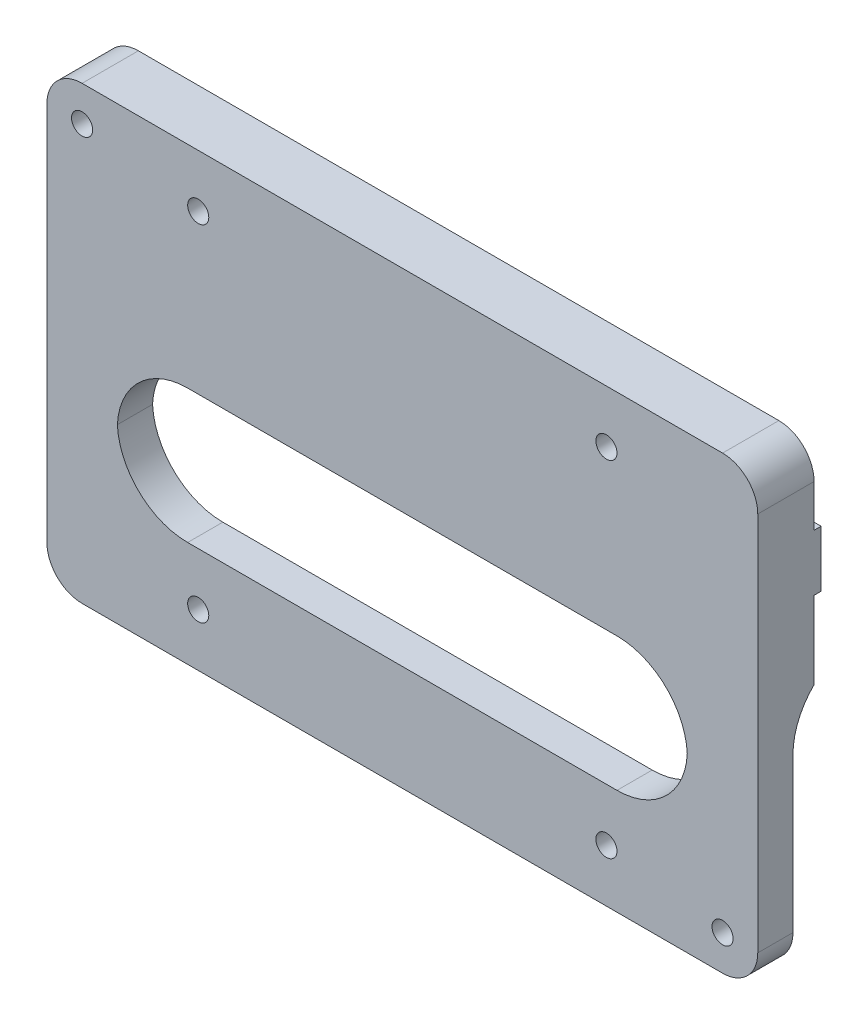
SolidWorks part; units mm, degrees
ref_plane "Top Plane" through (0, 0, 0) normal (0, 0, 1) x (1, 0, 0)
ref_plane "Right Plane" through (0, 0, 0) normal (0, 1, 0) x (1, 0, 0)
ref_plane "Front Plane" through (0, 0, 0) normal (1, 0, 0) x (0, 0, -1)
sketch "Sketch1" plane through (0, 0, 0) normal (0, 0, 1) x (1, 0, 0)
  line L0 (-50.5, 27) -> (-45.5, 27) construction
  line L1 (-29, -24.5) -> (29, -24.5) construction
  line L2 (-29, -24.5) -> (-29, 24.5) construction
  line L3 (-29, 24.5) -> (29, 24.5) construction
  line L4 (29, -24.5) -> (29, 24.5) construction
  line L5 (-29, -24.5) -> (29, 24.5) construction
  line L6 (-29, 24.5) -> (29, -24.5) construction
  line L7 (-50.5, -32) -> (50.5, -32)
  line L8 (-50.5, -32) -> (-50.5, 32)
  line L9 (-50.5, 32) -> (50.5, 32)
  line L10 (50.5, -32) -> (50.5, 32)
  line L11 (-50.5, -32) -> (50.5, 32) construction
  line L12 (-50.5, 32) -> (50.5, -32) construction
  line L13 (-45.5, 27) -> (-45.5, 32) construction
  line L14 (-45.5, 27) -> (45.5, -27) construction
  circle A0 centre (-29, 24.5) radius 1.5
  circle A1 centre (29, 24.5) radius 1.5
  circle A2 centre (29, -24.5) radius 1.5
  circle A3 centre (-29, -24.5) radius 1.5
  circle A4 centre (45.5, -27) radius 1.5
  circle A5 centre (-45.5, 27) radius 1.5
  point P0 (0, 0)
  point P10 (0, 0)
  dimension "D3" = 3
  dimension "D4" = 20
  dimension "D6" = 3
  dimension "D1" = 49
  dimension "D2" = 58
  dimension "D5" = 6
  dimension "D7" = 5
extrude "Boss-Extrude1" add sketch "Sketch1" along normal blind 8
sketch "Sketch2" plane through (-50.5, -4.5, 0) normal (-1, 0, 0) x (0, 1, 0)
  line L1 (17.5, 0) -> (25.5, 0)
  line L2 (17.5, 0) -> (17.5, 1)
  line L3 (17.5, 1) -> (25.5, 1)
  line L4 (25.5, 0) -> (25.5, 1)
  line L5 (36.5, 0) -> (-27.5, 0) construction
  point P4 (14.5, 0)
  point P6 (16.3891, 1)
  point P8 (21.5, 1)
  dimension "D1" = 15
  dimension "D2" = 8
  dimension "D3" = 1
extrude "Boss-Extrude2" add sketch "Sketch2" against normal up to surface (101 mm away) up to face at (50.5, 0, 4)
fillet "Fillet1" radius 5 4 edges at (-50.5, -32, 4) (-50.5, 32, 4) (50.5, -32, 4) (50.5, 32, 4)
sketch "Sketch3" plane through (0, 0, 0) normal (0, 0, -1) x (-1, 0, 0)
  line L0 (40.5, 2) -> (-40.5, 2)
  line L2 (-40.5, 2) -> (-40.5, -17)
  line L3 (-40.5, -17) -> (40.5, -17)
  line L4 (40.5, -17) -> (40.5, 2)
  line L5 (-50.5, -27) -> (-50.5, 13) construction
  line L7 (45.5, -32) -> (-45.5, -32) construction
  line L8 (-45.5, 32) -> (45.5, 32) construction
  line L9 (50.5, 27) -> (50.5, -27) construction
  dimension "D1" = 30
  dimension "D2" = 10
  dimension "D3" = 10
  dimension "D4" = 15
extrude "Cut-Extrude1" cut sketch "Sketch3" against normal through all
fillet "Fillet2" radius 10 4 edges at (40.5, -17, 4) (-40.5, -17, 4) (40.5, 2, 4) (-40.5, 2, 4)
sketch "Sketch4" plane through (50.5, -18.5, 0) normal (-1, 0, 0) x (0, 1, 0)
  line L1 (20.5, 0) -> (-13.5, 0)
  line L2 (20.5, 0) -> (20.5, -3)
  line L3 (20.5, -3) -> (-13.5, -3)
  line L4 (-13.5, 0) -> (-13.5, -3)
  line L7 (-8.5, 0) -> (31.5, 0) construction
  line L8 (-8.5, -8) -> (45.5, -8) construction
  point P6 (-5.3394, 0)
  point P7 (25.3006, 0)
  point P9 (-14.7544, 0)
  point P11 (0, 0)
  point P12 (0, 0)
  dimension "D1" = 5
  dimension "D2" = 30
extrude "Cut-Extrude2" cut sketch "Sketch4" along normal through all
fillet "Fillet3" radius 10 2 edges at (-40.5, 2, 3) (40.5, 2, 3)
